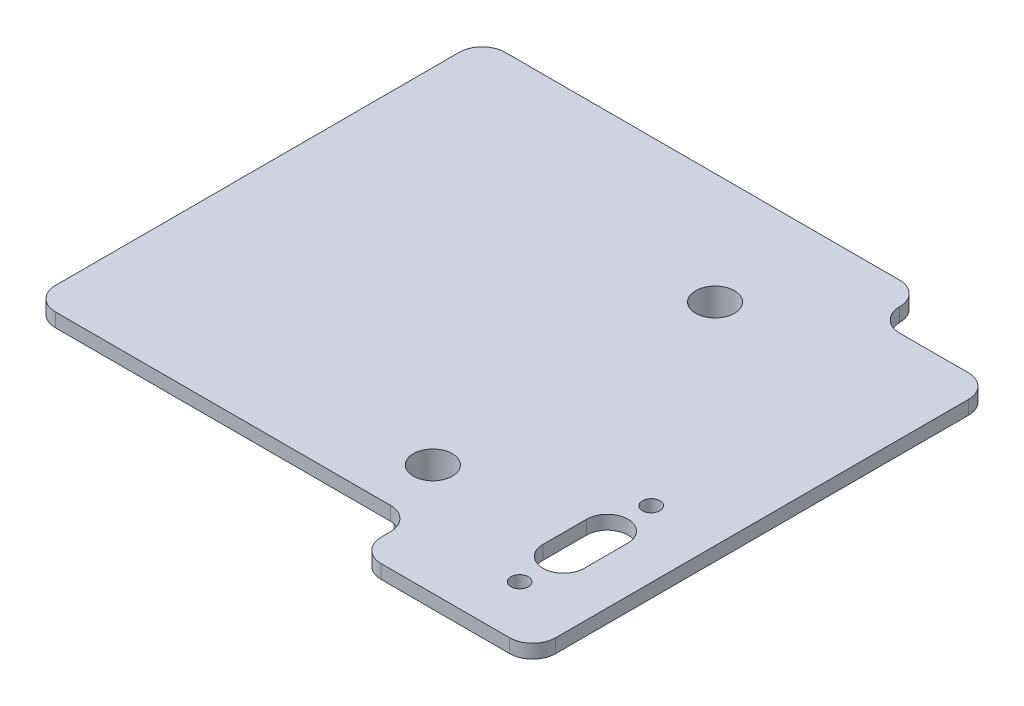
SolidWorks part; units mm, degrees
ref_plane "Front Plane" through (0, 0, 0) normal (0, 0, 1) x (1, 0, 0)
ref_plane "Top Plane" through (0, 0, 0) normal (0, 1, 0) x (1, 0, 0)
ref_plane "Right Plane" through (0, 0, 0) normal (1, 0, 0) x (0, 0, -1)
sketch "Sketch1" plane through (0, 0, 0) normal (0, 1, 0) x (1, 0, 0)
  line L0 (0, 0) -> (83, 0)
  line L1 (83, 0) -> (83, -12)
  line L2 (83, -12) -> (121, -12)
  line L3 (121, -12) -> (121, 88)
  line L5 (0, 98) -> (0, 0)
  line L6 (0, 43) -> (121, 43) construction
  line L7 (75, 73.75) -> (75, 12.25) construction
  line L8 (0, 98) -> (96, 98)
  line L9 (96, 98) -> (96, 88)
  line L10 (96, 88) -> (121, 88)
  line L11 (86.8502, -12) -> (86.8502, 98) construction
  point P11 (75, 43)
  point P13 (75, 73.75)
  point P14 (75, 12.25)
  point P18 (86.8502, 43)
  dimension "D1" = 121
  dimension "D2" = 110
  dimension "D3" = 38
  dimension "D4" = 12
  dimension "D5" = 61.5
  dimension "D6" = 8
  dimension "D7" = 10
  dimension "D8" = 25
extrude "plate" add sketch "Sketch1" along normal blind 3
sketch "Sketch2" plane through (0, 3, 0) normal (0, 1, 0) x (1, 0, 0)
  circle A0 centre (75, 73.75) radius 6
  circle A1 centre (75, 12.25) radius 6
  dimension "D1" = 12
extrude "mount posts" add sketch "Sketch2" against normal blind 22
sketch "Sketch3" plane through (0, 3, 0) normal (0, 1, 0) x (1, 0, 0)
  circle A0 centre (75, 73.75) radius 4.25
  circle A1 centre (75, 12.25) radius 4.25
  dimension "D1" = 8.5
extrude "mount cbore" cut sketch "Sketch3" against normal blind 19.5
hole_wizard "#8 Clearance Hole1" positions "Sketch4" profile "Sketch5" hole size "#8" standard "ANSI Inch" end condition through all
sketch "Sketch4" plane through (0, -16.5, 0) normal (0, 1, 0) x (1, 0, 0)
  circle A0 centre (75, 12.25) radius 4.25 construction
  circle A1 centre (75, 73.75) radius 4.25 construction
  point P0 (75, 73.75)
  point P2 (75, 12.25)
sketch "Sketch5" plane through (75, -16.5, -73.75) normal (1, 0, 0) x (0, 0, 1)
  line L0 (0, 0) -> (0, 2.5)
  line L1 (0, 2.5) -> (2.2479, 2.5)
  line L2 (2.2479, 2.5) -> (2.2479, 0)
  line L5 (2.2479, 0) -> (0, 0)
  line L11 (0, -6.35) -> (0, 107.95) construction
  dimension "Thru Hole Dia." = 4.4958
  dimension "Thru Hole Depth" = 2.5
ref_plane "mid plane" through (0, 0, -43) normal (0, 0, -1) x (1, 0, 0)
sketch "Sketch8" plane through (0, 0, -43) normal (0, 0, -1) x (1, 0, 0)
  line L0 (45.25, 0) -> (46.85, 0)
  line L1 (0, 0) -> (121, 0) construction
  line L2 (45.25, 0) -> (43.5, 29)
  line L3 (43.5, 29) -> (45.1, 29)
  line L4 (45.1, 29) -> (46.85, 0)
  line L5 (40, 0) -> (40, 41.9178) construction
  point P9 (44.3, 29)
  dimension "D1" = 1.6
  dimension "D2" = 3.5
  dimension "D3" = 29
  dimension "D4" = 5.25
  dimension "D5" = 40
revolve "foot" add sketch "Sketch8" angle 360 about L5
fillet "Fillet1" radius 1.5 2 edges at (40, 0, -37.75) (40, 0, -36.15)
sketch "Sketch7" plane through (0, 3, 0) normal (0, 1, 0) x (1, 0, 0)
  line L0 (106.5, 87.7375) -> (106.5, 106.2625) construction
  line L1 (121, -12) -> (121, 88) construction
  line L2 (83, -12) -> (121, -12) construction
  line L3 (115, 14) -> (98, 14) construction
  line L4 (102, 9.2375) -> (102, 18.7625)
  line L5 (98, -6) -> (98, 34) construction
  line L6 (98, -6) -> (115, -6) construction
  line L7 (115, -6) -> (115, 34) construction
  line L8 (98, 34) -> (115, 34) construction
  line L9 (98, -6) -> (115, 34) construction
  line L10 (115, -6) -> (98, 34) construction
  line L11 (111, 9.2375) -> (111, 18.7625)
  circle A0 centre (106.5, 9.2375) radius 4.5 construction
  circle A1 centre (106.5, 18.7625) radius 4.5 construction
  arc A2 (102, 9.2375) -> (111, 9.2375) centre (106.5, 9.2375) ccw
  arc A3 (102, 18.7625) -> (111, 18.7625) centre (106.5, 18.7625) cw
  circle A4 centre (106.5, 28.34) radius 1.9
  circle A5 centre (106.5, -0.34) radius 1.9
  point P16 (106.5, 14)
  point P19 (102, -12)
  dimension "D2" = 9.525
  dimension "D5" = 9
  dimension "D6" = 3.8
  dimension "D1" = 40
  dimension "D3" = 6
  dimension "D4" = 17
  dimension "D7" = 28.68
  dimension "D8" = 6
extrude "terminal strip" cut sketch "Sketch7" against normal through all
chamfer "Chamfer1" distance 3 angle 45 2 edges at (75, -16.5, -69.5) (75, -16.5, -8)
chamfer "Chamfer2" distance 1 angle 45 2 edges at (75, -19, -6.25) (75, -19, -67.75)
fillet "Fillet3" radius 1.5 2 edges at (75, 0, -67.75) (75, 0, -6.25)
fillet "corners" radius 5 8 edges at (0, 1.5, -98) (96, 1.5, -98) (96, 1.5, -88) (121, 1.5, -88) (121, 1.5, 12) (83, 1.5, 12) (83, 1.5, 0) (0, 1.5, 0)
